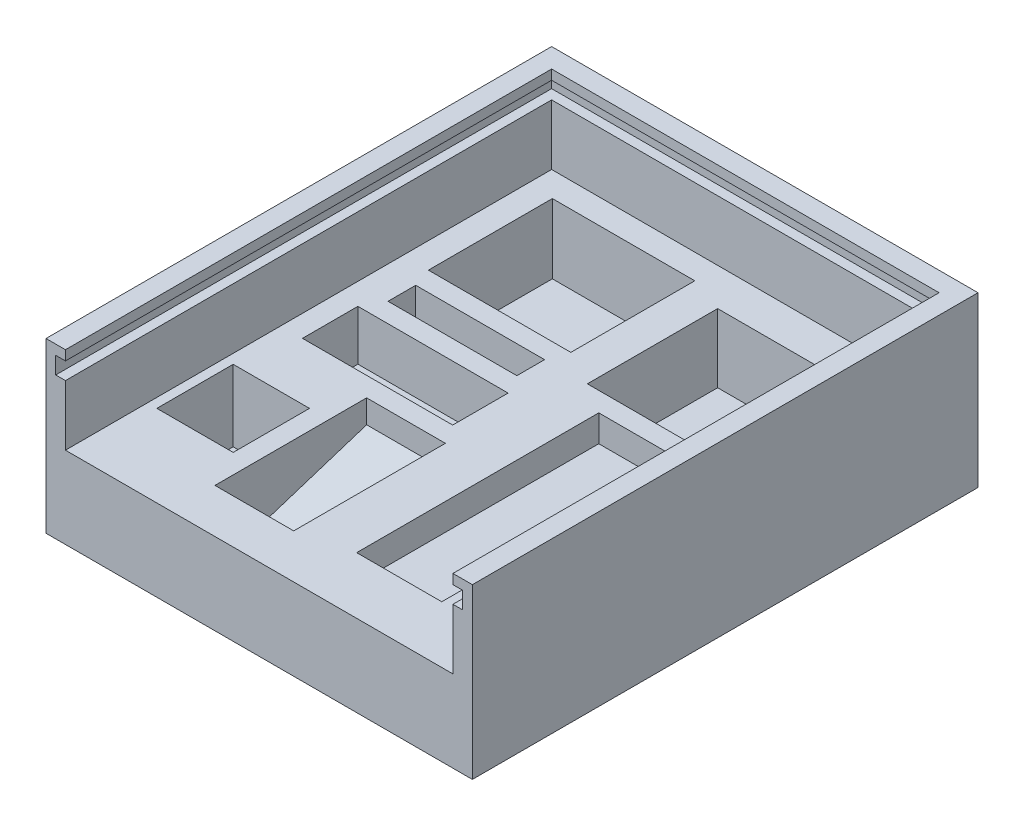
SolidWorks part; units mm, degrees
ref_plane "Front Plane" through (0, 0, 0) normal (0, 0, 1) x (1, 0, 0)
ref_plane "Top Plane" through (0, 0, 0) normal (0, 1, 0) x (1, 0, 0)
ref_plane "Right Plane" through (0, 0, 0) normal (1, 0, 0) x (0, 0, -1)
sketch "Sketch1" plane through (0, 0, 0) normal (0, 1, 0) x (1, 0, 0)
  line L0 (-41.85, -51) -> (-43.85, -51)
  line L1 (-41.85, -51) -> (41.85, -51)
  line L2 (-41.85, -51) -> (-41.85, 51)
  line L3 (-41.85, 51) -> (41.85, 51)
  line L4 (41.85, -51) -> (41.85, 51)
  line L5 (-41.85, -51) -> (41.85, 51) construction
  line L6 (-41.85, 51) -> (41.85, -51) construction
  line L7 (-43.85, -51) -> (-43.85, 53)
  line L8 (-43.85, 53) -> (43.85, 53)
  line L9 (43.85, 53) -> (43.85, -51)
  line L10 (-41.85, -49) -> (41.85, -49)
  line L12 (-2, -51) -> (2, -51)
  line L13 (-2, -51) -> (-2, 51)
  line L14 (43.85, -51) -> (41.85, -51)
  line L15 (-2, 51) -> (2, 51)
  line L16 (2, -51) -> (2, 51)
  line L17 (-2, -51) -> (2, 51) construction
  line L18 (-2, 51) -> (2, -51) construction
  line L19 (2, 41.3) -> (28.6, 41.3)
  line L20 (2, 41.3) -> (2, 14.5)
  line L21 (2, 14.5) -> (28.6, 14.5)
  line L22 (28.6, 41.3) -> (28.6, 14.5)
  line L23 (2, 14.5) -> (28.6, 14.5)
  line L24 (2, 14.5) -> (2, 10.5)
  line L25 (2, 10.5) -> (28.6, 10.5)
  line L27 (2, 10.5) -> (28.6, 10.5)
  line L28 (2, 10.5) -> (2, -39.3)
  line L29 (2, -39.3) -> (28.6, -39.3)
  line L30 (28.6, 10.5) -> (28.6, -39.3)
  line L31 (8.35, 10.5) -> (25.85, 10.5)
  line L32 (8.35, 10.5) -> (8.35, -39.3)
  line L33 (8.35, -39.3) -> (25.85, -39.3)
  line L34 (25.85, 10.5) -> (25.85, -39.3)
  line L35 (-2, -10.7) -> (-37.9, -10.7)
  line L36 (-2, -10.7) -> (-2, -41.9)
  line L37 (-2, -41.9) -> (-37.9, -41.9)
  line L38 (-37.9, -10.7) -> (-37.9, -41.9)
  line L39 (-2, -10.7) -> (-37.9, -10.7)
  line L40 (-2, -10.7) -> (-2, -6.7)
  line L41 (-2, -6.7) -> (-37.9, -6.7)
  line L43 (-2, -6.7) -> (-37.9, -6.7)
  line L44 (-2, -6.7) -> (-2, 4.7)
  line L45 (-2, 4.7) -> (-37.9, 4.7)
  line L46 (-37.9, -6.7) -> (-37.9, 4.7)
  line L47 (-2, 4.7) -> (-37.9, 4.7)
  line L48 (-2, 4.7) -> (-2, 8.7)
  line L49 (-2, 8.7) -> (-37.9, 8.7)
  line L51 (-2, 8.7) -> (-37.9, 8.7)
  line L52 (-2, 8.7) -> (-2, 14.4)
  line L53 (-2, 14.4) -> (-37.9, 14.4)
  line L54 (-37.9, 8.7) -> (-37.9, 14.4)
  line L55 (-2, 14.4) -> (-37.9, 14.4)
  line L56 (-2, 14.4) -> (-2, 18.4)
  line L57 (-2, 18.4) -> (-37.9, 18.4)
  line L59 (-2, 18.4) -> (-37.9, 18.4)
  line L60 (-2, 18.4) -> (-2, 43.9)
  line L61 (-2, 43.9) -> (-37.9, 43.9)
  line L62 (-37.9, 18.4) -> (-37.9, 43.9)
  line L63 (-34.6, 43.9) -> (-5.3, 43.9)
  line L64 (-34.6, 43.9) -> (-34.6, 18.4)
  line L65 (-34.6, 18.4) -> (-5.3, 18.4)
  line L66 (-5.3, 43.9) -> (-5.3, 18.4)
  line L67 (-33.2, 14.4) -> (-6.7, 14.4)
  line L68 (-33.2, 14.4) -> (-33.2, 8.7)
  line L69 (-33.2, 8.7) -> (-6.7, 8.7)
  line L70 (-6.7, 14.4) -> (-6.7, 8.7)
  line L71 (-35.4, 4.7) -> (-4.5, 4.7)
  line L72 (-35.4, 4.7) -> (-35.4, -6.7)
  line L73 (-35.4, -6.7) -> (-4.5, -6.7)
  line L74 (-4.5, 4.7) -> (-4.5, -6.7)
  line L75 (-32.1208, -10.7) -> (-18.2, -10.7)
  line L77 (-32.1208, -41.9) -> (-18.2, -41.9)
  line L78 (-18.2, -10.7) -> (-18.2, -41.9)
  line L79 (-22.2, -10.7) -> (-4.2208, -10.7)
  line L80 (-22.2, -10.7) -> (-22.2, -41.9)
  line L81 (-22.2, -41.9) -> (-4.2208, -41.9)
  line L83 (-37.9, -18.45) -> (-22.2, -18.45)
  line L84 (-37.9, -18.45) -> (-37.9, -34.15)
  line L85 (-37.9, -34.15) -> (-22.2, -34.15)
  line L86 (-22.2, -18.45) -> (-22.2, -34.15)
  point P0 (0, 0)
  point P11 (0, 0)
  dimension "D1" = 83.7
  dimension "D2" = 102
  dimension "D3" = 2
  dimension "D4" = 2
  dimension "D5" = 2
  dimension "D6" = 2
  dimension "D7" = 4
  dimension "D8" = 26.6
  dimension "D9" = 26.8
  dimension "D10" = 4
  dimension "D11" = 49.8
  dimension "D12" = 17.5
  dimension "D13" = 6.35
  dimension "D14" = 35.9
  dimension "D15" = 31.2
  dimension "D16" = 4
  dimension "D17" = 4
  dimension "D18" = 4
  dimension "D19" = 11.4
  dimension "D20" = 5.7
  dimension "D21" = 25.5
  dimension "D22" = 29.3
  dimension "D23" = 3.3
  dimension "D24" = 4.7
  dimension "D25" = 26.5
  dimension "D26" = 2.5
  dimension "D27" = 30.9
  dimension "D28" = 16.2
  dimension "D29" = 4
  dimension "D30" = 7.75
  dimension "D31" = 15.7
  dimension "D32" = 7.1
  dimension "D33" = 9.7
extrude "Boss-Extrude1" add sketch "Sketch1" along normal blind 0.7 contours L70 L55 L68 L51 region at (-19.95, 0, -11.55)
extrude "Boss-Extrude2" add sketch "Sketch1<3>" along normal blind 4.5 separate body contours L74 L47 L72 L43 region at (-19.95, 0, 1)
sketch "Sketch1<3>" plane through (0, 0, 0) normal (0, 1, 0) x (1, 0, 0) same geometry as "Sketch1"
extrude "Boss-Extrude3" add sketch "Sketch1<4>" along normal blind 0.5 separate body contours L66 L61 L64 L59 region at (-19.95, 0, -31.15)
sketch "Sketch1<4>" plane through (0, 0, 0) normal (0, 1, 0) x (1, 0, 0) same geometry as "Sketch1"
extrude "Boss-Extrude4" add sketch "Sketch1<5>" along normal blind 0.1 separate body contours L38 L85 L80 L83 region at (-30.05, 0, 26.3)
sketch "Sketch1<5>" plane through (0, 0, 0) normal (0, 1, 0) x (1, 0, 0) same geometry as "Sketch1"
extrude "Boss-Extrude6" add sketch "Sketch1<7>" along normal blind 9.3 separate body contours L34 L27 L32 L29 region at (17.1, 0, 14.4)
sketch "Sketch1<7>" plane through (0, 0, 0) normal (0, 1, 0) x (1, 0, 0) same geometry as "Sketch1"
extrude "Boss-Extrude7" add sketch "Sketch1<8>" along normal blind 0.7 separate body contours L22 L19 L16 L21 region at (15.3, 0, -27.9)
sketch "Sketch1<8>" plane through (0, 0, 0) normal (0, 1, 0) x (1, 0, 0) same geometry as "Sketch1"
extrude "Boss-Extrude8" add sketch "Sketch1<10>" along normal blind 14.8 contours L39 L80 L37 L78 | L57 L59 L62 L61 L13 L3 L2 L10 L37 L77 L38 L35 L75 L39 L41 L43 L46 L45 L47 L49 L51 L54 L53 L55 | L85 L38 L37 L77 L80 | L38 L83 L80 L75 L35 | L72 L45 L46 L43 | L45 L74 L41 L13 | L53 L70 L49 L13 | L68 L53 L54 L51 | L64 L61 L62 L59 | L61 L66 L57 L13 | L10 L16 L3 L13 | L25 L27 L30 L29 L16 L10 L4 L3 L19 L22 L21 | L32 L25 L16 L29 | L25 L34 L29 L30 region at (-40.7735, 0, -1) region at (0, 0, -1) region at (28.8566, 0, -1.6283) region at (5.175, 0, 14.4) region at (-3.65, 0, -31.15) region at (-3.25, 0, 1) region at (-20.2, 0, 26.3) region at (27.225, 0, 14.4) region at (-30.05, 0, 38.025) region at (-4.35, 0, -11.55) region at (-36.25, 0, -31.15) region at (-36.65, 0, 1) region at (-30.05, 0, 14.575) region at (-35.55, 0, -11.55)
sketch "Sketch1<10>" plane through (0, 0, 0) normal (0, 1, 0) x (1, 0, 0) same geometry as "Sketch1"
extrude "Boss-Extrude9" add sketch "Sketch1<11>" against normal blind 2 contours L14 L9 L8 L7 L0 L2 L3 L4 | L25 L27 L30 L29 L16 L10 L4 L3 L19 L22 L21 | L22 L19 L16 L21 | L35 L39 L78 L37 L13 | L25 L34 L29 L30 | L34 L27 L32 L29 | L32 L25 L16 L29 | L10 L16 L3 L13 | L57 L59 L62 L61 L13 L3 L2 L10 L37 L77 L38 L35 L75 L39 L41 L43 L46 L45 L47 L49 L51 L54 L53 L55 | L66 L61 L64 L59 | L74 L47 L72 L43 | L70 L55 L68 L51 | L61 L66 L57 L13 | L64 L61 L62 L59 | L68 L53 L54 L51 | L53 L70 L49 L13 | L45 L74 L41 L13 | L72 L45 L46 L43 | L38 L85 L80 L83 | L38 L83 L80 L75 L35 | L39 L80 L37 L78 | L85 L38 L37 L77 L80 region at (-42.85, 0, 49.6396) region at (-40.7735, 0, -1) region at (0, 0, -1) region at (28.8566, 0, -1.6283) region at (-10.1, 0, 26.3) region at (5.175, 0, 14.4) region at (-3.65, 0, -31.15) region at (17.1, 0, 14.4) region at (-3.25, 0, 1) region at (-20.2, 0, 26.3) region at (15.3, 0, -27.9) region at (-19.95, 0, -31.15) region at (27.225, 0, 14.4) region at (-19.95, 0, 1) region at (-30.05, 0, 38.025) region at (-4.35, 0, -11.55) region at (-36.25, 0, -31.15) region at (-36.65, 0, 1) region at (-30.05, 0, 14.575) region at (-30.05, 0, 26.3) region at (-19.95, 0, -11.55) region at (-35.55, 0, -11.55)
sketch "Sketch1<11>" plane through (0, 0, 0) normal (0, 1, 0) x (1, 0, 0) same geometry as "Sketch1"
extrude "Boss-Extrude10" add sketch "Sketch1<12>" against normal blind 2 contours L1 L13 L10 L2 | L1 L16 L10 L13 | L16 L1 L4 L10 region at (-21.925, 0, 50) region at (0, 0, 50) region at (21.925, 0, 50)
sketch "Sketch1<12>" plane through (0, 0, 0) normal (0, 1, 0) x (1, 0, 0) same geometry as "Sketch1"
extrude "Boss-Extrude11" add sketch "Sketch1<13>" along normal blind 27.2 contours L14 L9 L8 L7 L0 L2 L3 L4 region at (-42.85, 0, 49.6396)
sketch "Sketch1<13>" plane through (0, 0, 0) normal (0, 1, 0) x (1, 0, 0) same geometry as "Sketch1"
extrude "Boss-Extrude12" add sketch "Sketch1<14>" along normal blind 14.8 contours L1 L13 L10 L2 | L1 L16 L10 L13 | L16 L1 L4 L10 region at (-21.925, 0, 50) region at (0, 0, 50) region at (21.925, 0, 50)
sketch "Sketch1<14>" plane through (0, 0, 0) normal (0, 1, 0) x (1, 0, 0) same geometry as "Sketch1"
sketch "Sketch2" plane through (0, 14.8, 0) normal (0, 1, 0) x (1, 0, 0)
  line L0 (-39.85, -51) -> (-39.85, 49)
  line L1 (-41.85, -51) -> (41.85, -51) construction
  line L2 (-39.85, 49) -> (39.85, 49)
  line L3 (39.85, 49) -> (39.85, -51)
  line L4 (-41.85, -51) -> (-41.85, 51) construction
  line L5 (-41.85, 51) -> (41.85, 51) construction
  line L6 (41.85, -51) -> (41.85, 51) construction
  line L7 (-39.85, -51) -> (-41.85, -51)
  line L8 (-41.85, -51) -> (-41.85, 51)
  line L9 (-41.85, 51) -> (41.85, 51)
  line L10 (41.85, 51) -> (41.85, -51)
  line L11 (41.85, -51) -> (39.85, -51)
  dimension "D1" = 2
  dimension "D2" = 2
  dimension "D3" = 2
extrude "Boss-Extrude13" add sketch "Sketch2" along normal blind 12.4
extrude "Boss-Extrude14" add sketch "Sketch1<15>" along normal blind 32.7 contours L14 L9 L8 L7 L0 L2 L3 L4 region at (-42.85, 0, 49.6396)
sketch "Sketch1<15>" plane through (0, 0, 0) normal (0, 1, 0) x (1, 0, 0) same geometry as "Sketch1"
sketch "Sketch3" plane through (0, 32.7, 0) normal (0, 1, 0) x (1, 0, 0)
  line L0 (-41.85, -51) -> (-39.85, -51)
  line L1 (-39.85, -51) -> (-39.85, 49)
  line L2 (-39.85, 49) -> (39.85, 49)
  line L3 (39.85, 49) -> (39.85, -51)
  line L4 (39.85, -51) -> (41.85, -51)
  line L5 (41.85, -51) -> (41.85, 51)
  line L6 (41.85, 51) -> (-41.85, 51)
  line L7 (-41.85, 51) -> (-41.85, -51)
  dimension "D1" = 2
  dimension "D2" = 2
  dimension "D3" = 2
extrude "Boss-Extrude15" add sketch "Sketch3" against normal blind 2
sketch "Sketch4" plane through (-18.2, 0, 0) normal (1, 0, 0) x (0, 0, -1)
  line L0 (-10.7, 10) -> (-10.7, 0)
  line L1 (-10.7, 14.8) -> (-10.7, 0) construction
  line L2 (-10.7, 0) -> (-41.9, 0)
  line L3 (-41.9, 0) -> (-10.7, 10)
  line L4 (-10.7, 0) -> (-41.9, 0) construction
  point P7 (-10.7, 13.2706)
  dimension "D1" = 10
extrude "Boss-Extrude16" add sketch "Sketch4" along normal blind 16.2
